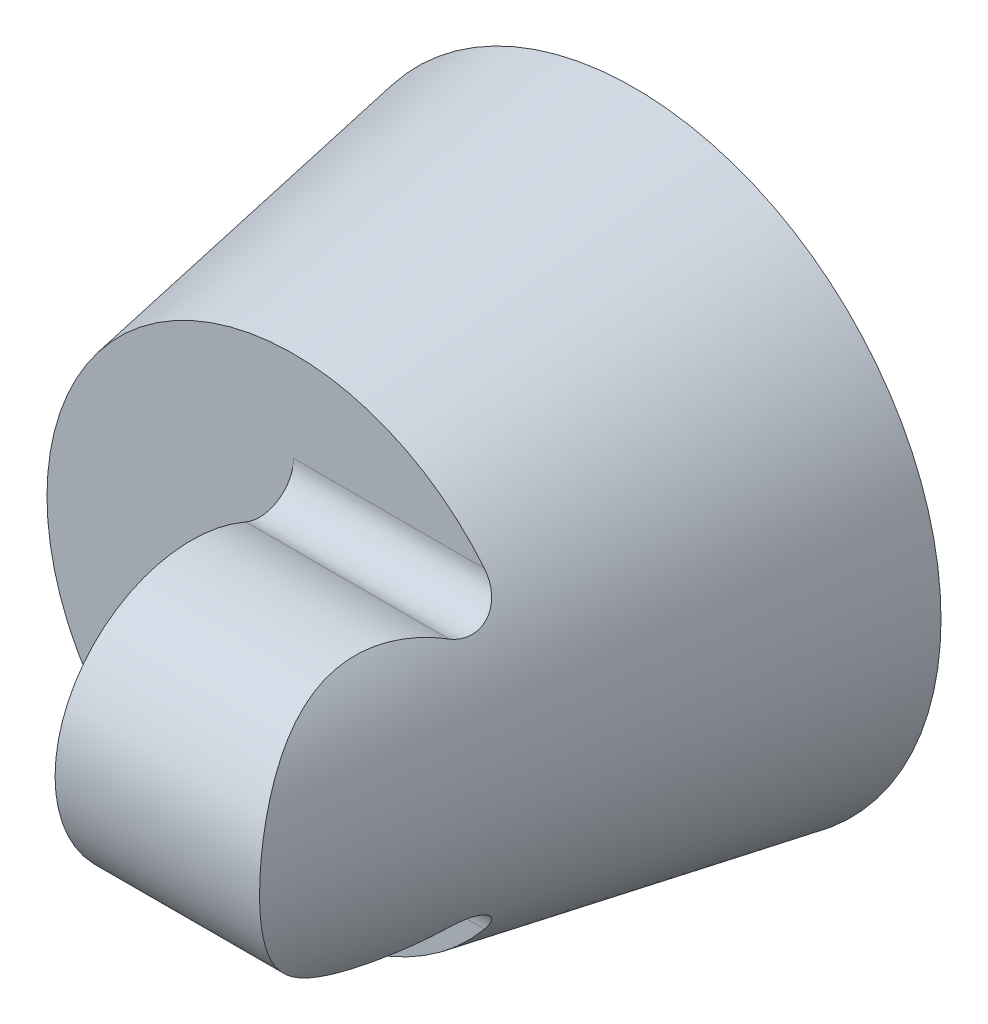
SolidWorks part; units mm, degrees
ref_plane "Plan de face" through (0, 0, 0) normal (0, 0, 1) x (1, 0, 0)
ref_plane "Plan de dessus" through (0, 0, 0) normal (0, 1, 0) x (1, 0, 0)
ref_plane "Plan de droite" through (0, 0, 0) normal (1, 0, 0) x (0, 0, -1)
sketch "Esquisse1" plane through (0, 0, 0) normal (0, 0, 1) x (1, 0, 0)
  circle A0 centre (0, 0) radius 45
  dimension "D1" = 90
extrude "Boss.-Extru.1" add sketch "Esquisse1" along normal blind 50 draft 10
sketch "Esquisse2" plane through (0, 0, 0) normal (1, 0, 0) x (0, 0, -1)
  line L1 (-50, 36.1837) -> (-50, -36.1837) construction
  circle A0 centre (-65, 0) radius 20
  point P2 (0, 0)
  dimension "D1" = 40
  dimension "D2" = 15
extrude "Boss.-Extru.2" add sketch "Esquisse2" along normal up to surface (37.0653 mm away) up to face at (36.1837, 0, 50)
fillet "Congé1" radius 5 2 edges at (16.8394, -13.2288, 50) (16.8394, 13.2288, 50)
